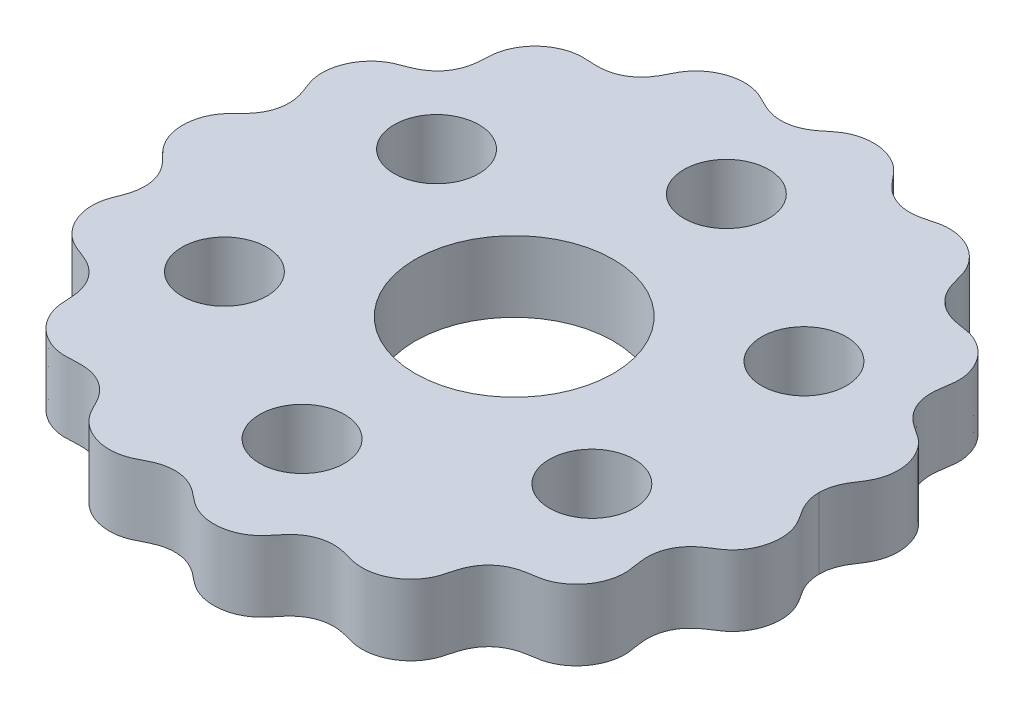
SolidWorks part; units mm, degrees
ref_plane "Front Plane" through (0, 0, 0) normal (0, 0, 1) x (1, 0, 0)
ref_plane "Top Plane" through (0, 0, 0) normal (0, 1, 0) x (1, 0, 0)
ref_plane "Right Plane" through (0, 0, 0) normal (1, 0, 0) x (0, 0, -1)
sketch "Sketch1" plane through (0, 0, 0) normal (0, 1, 0) x (1, 0, 0)
  spline S0 degree 4 poles (44.5984, 12.4944) (44.832, 12.1879) (45.2512, 11.5384) (45.7237, 10.4856) (45.9984, 9.1724) (46.03, 8.0346) (45.9105, 7.0216) (45.7203, 6.2632) (45.4573, 5.5829) (45.1464, 4.9823) (44.8648, 4.5205) (44.5648, 4.0709) (44.2669, 3.6199) (44.0083, 3.1913) (43.7929, 2.7844) (43.6185, 2.4022) (43.4802, 2.0484) (43.3629, 1.687) (43.2797, 1.3651) (43.2227, 1.0859) (43.1851, 0.8518) (43.1609, 0.6624) (43.145, 0.4992) (43.1351, 0.3578) (43.1294, 0.2322) (43.1264, 0.1298) (43.1245, 0.0125) (43.1252, -0.0782) (43.1286, -0.2195) (43.135, -0.3523) (43.1419, -0.4548) (43.1529, -0.582) (43.1699, -0.7377) (43.1951, -0.92) (43.231, -1.126) (43.274, -1.3311) (43.3366, -1.5852) (43.4549, -1.9872) (43.66, -2.5262) (44.0033, -3.2085) (44.4867, -3.963) (45.0117, -4.7244) (45.4649, -5.567) (45.8298, -6.5835) (46.0376, -7.77) (46.0189, -9.1082) (45.6992, -10.542) (45.1324, -11.7906) (44.3914, -12.8211) (43.5537, -13.6249) (42.6868, -14.2187) (41.8472, -14.7237) (41.113, -15.2701) (40.3565, -15.9849) (39.644, -16.9209) (39.0655, -18.1762) (38.8218, -19.6149) (38.8837, -20.8087) (39.0365, -21.7287) (39.15, -22.395) (39.2185, -22.9317) (39.2565, -23.6072) (39.2077, -24.5293) (38.9566, -25.6753) (38.3836, -26.9664) (37.4913, -28.188) (36.4562, -29.1122) (35.3715, -29.7513) (34.3004, -30.1449) (33.2968, -30.3406) (32.3424, -30.4567) (31.4554, -30.643) (30.6507, -30.9105) (29.9366, -31.2505) (29.1129, -31.7819) (28.2521, -32.581) (27.6169, -33.5017) (27.1961, -34.4634) (26.9571, -35.2233) (26.8167, -35.7523) (26.6832, -36.2827) (26.5312, -36.8085) (26.2971, -37.4517) (25.8833, -38.2906) (25.1883, -39.2563) (24.1248, -40.2304) (22.7782, -41.008) (21.4029, -41.4417) (20.2189, -41.5611) (19.2857, -41.4995) (18.4763, -41.358) (17.6848, -41.1398) (16.6569, -40.8411) (15.3426, -40.6571) (13.8913, -40.7732) (12.5919, -41.238) (11.5918, -41.8684) (10.8098, -42.5627) (10.2051, -43.2377) (9.6272, -44.0062) (8.9561, -44.7774) (8.0796, -45.5082) (6.9838, -46.1281) (5.6659, -46.5624) (4.1618, -46.7244) (2.7571, -46.5751) (1.6391, -46.2195) (0.8162, -45.8007) (0.2502, -45.4301) (-0.1804, -45.1024) (-0.7006, -44.671) (-1.421, -44.0787) (-2.4239, -43.4281) (-3.7917, -42.9198) (-5.168, -42.7932) (-6.3349, -42.9422) (-7.3322, -43.24) (-8.1725, -43.6026) (-9.0297, -44.0772) (-9.9774, -44.531) (-11.0923, -44.8546) (-12.3553, -44.9811) (-13.7375, -44.8459) (-15.1718, -44.3905) (-16.3918, -43.6927) (-17.2693, -42.9227) (-17.8533, -42.2132) (-18.2222, -41.6499) (-18.4839, -41.1793) (-18.7839, -40.5772) (-19.1955, -39.7455) (-19.8345, -38.7424) (-20.8622, -37.7122) (-22.2286, -36.9233) (-23.6346, -36.5484) (-24.8229, -36.4966) (-25.7489, -36.5559) (-26.4204, -36.5972) (-26.9588, -36.6058) (-27.631, -36.5681) (-28.5375, -36.417) (-29.643, -36.0421) (-30.8574, -35.3344) (-31.969, -34.32) (-32.7771, -33.1905) (-33.2991, -32.0336) (-33.5763, -30.9061) (-33.6571, -29.8585) (-33.6747, -28.8788) (-33.7808, -27.9699) (-34.0216, -26.9573) (-34.476, -25.8723) (-35.2738, -24.7436) (-36.3979, -23.8132) (-37.4628, -23.2699) (-38.3359, -22.9423) (-38.9696, -22.7074) (-39.4687, -22.4983) (-40.0727, -22.1935) (-40.8469, -21.6902) (-41.7138, -20.8998) (-42.5454, -19.758) (-43.1572, -18.3744) (-43.44, -17.0159) (-43.4511, -15.757) (-43.2564, -14.6325) (-42.9241, -13.6656) (-42.5475, -12.7809) (-42.2653, -11.9197) (-42.055, -10.8955) (-42.0167, -9.9082) (-42.1512, -8.933) (-42.4518, -8.0043) (-42.7822, -7.3039) (-43.24, -6.5824) (-43.8372, -5.8614) (-44.4706, -5.2544) (-45.0553, -4.6782) (-45.4944, -4.1525) (-45.8114, -3.7063) (-46.0684, -3.2686) (-46.2741, -2.8497) (-46.4358, -2.4552) (-46.5617, -2.0905) (-46.6535, -1.7655) (-46.7191, -1.4838) (-46.7651, -1.2471) (-46.7966, -1.0568) (-46.8229, -0.866) (-46.8439, -0.6732) (-46.8577, -0.507) (-46.8662, -0.3636) (-46.8712, -0.2362) (-46.8738, -0.132) (-46.8754, -0.0158) (-46.8748, 0.091) (-46.8703, 0.2911) (-46.8602, 0.4745) (-46.8449, 0.6629) (-46.8245, 0.8522) (-46.7991, 1.0403) (-46.7685, 1.2276) (-46.724, 1.4607) (-46.6604, 1.7382) (-46.5715, 2.0584) (-46.4496, 2.4181) (-46.2927, 2.8077) (-46.0929, 3.2223) (-45.843, 3.6565) (-45.5342, 4.1002) (-45.1056, 4.6236) (-44.5323, 5.1972) (-43.9, 5.7965) (-43.2951, 6.5085) (-42.8248, 7.2269) (-42.4804, 7.9319) (-42.1599, 8.8828) (-42.0135, 9.8922) (-42.0547, 10.922) (-42.228, 11.7337) (-42.3436, 12.1315) (-42.4074, 12.3284) knots 0 0 0 0 0 0.008419 0.016837 0.025005 0.029089 0.033173 0.039077 0.042029 0.044981 0.047933 0.050885 0.053837 0.056789 0.058863 0.060937 0.063011 0.065085 0.067158 0.068195 0.069232 0.070269 0.071306 0.071825 0.072343 0.072861 0.07338 0.074472 0.075017 0.075563 0.076135 0.076707 0.07785 0.078994 0.080138 0.081281 0.082425 0.084712 0.089287 0.093861 0.099069 0.104277 0.109486 0.114694 0.122573 0.130452 0.138512 0.146571 0.152296 0.158021 0.163745 0.16947 0.173713 0.177956 0.186442 0.195001 0.203561 0.209467 0.212421 0.215374 0.218327 0.22128 0.227187 0.235488 0.24379 0.251894 0.259998 0.265567 0.271137 0.276706 0.282275 0.286582 0.290889 0.295197 0.299504 0.307939 0.316375 0.319362 0.32235 0.325338 0.328326 0.331314 0.334302 0.340277 0.348703 0.357129 0.365555 0.373981 0.379956 0.382944 0.385932 0.391908 0.397883 0.406319 0.414754 0.423368 0.427675 0.431982 0.437552 0.443121 0.44869 0.45426 0.462364 0.470468 0.478769 0.487071 0.492978 0.495931 0.498884 0.501837 0.50479 0.510697 0.519257 0.527816 0.536302 0.540545 0.544788 0.550513 0.556237 0.561962 0.567686 0.575746 0.583806 0.592068 0.60033 0.606208 0.609147 0.612086 0.615025 0.617964 0.623842 0.63236 0.640878 0.649396 0.657914 0.663792 0.666731 0.66967 0.672609 0.675548 0.681426 0.689688 0.69795 0.70601 0.714069 0.719794 0.725519 0.731243 0.736968 0.741211 0.745454 0.75394 0.762499 0.771059 0.776965 0.779919 0.782872 0.785825 0.788778 0.794685 0.802986 0.811288 0.819392 0.827496 0.833065 0.838635 0.844204 0.849773 0.85408 0.858388 0.867002 0.871219 0.875437 0.879655 0.883873 0.889848 0.895824 0.898812 0.9018 0.904787 0.907775 0.909882 0.911988 0.914095 0.916201 0.917254 0.918308 0.919361 0.920414 0.921467 0.92252 0.923047 0.923574 0.9241 0.924627 0.925664 0.9267 0.927737 0.928773 0.92981 0.930846 0.931883 0.93292 0.934993 0.937066 0.939139 0.941212 0.944163 0.947114 0.950065 0.953016 0.958918 0.96482 0.969093 0.973365 0.977638 0.981911 0.990955 0.995478 1 1 1 1 1 construction
  spline S1 degree 4 poles (43.125, 0) (43.125, -0.0425) (43.1258, -0.1053) (43.1286, -0.2195) (43.135, -0.3523) (43.1419, -0.4548) (43.1529, -0.582) (43.1699, -0.7377) (43.1951, -0.92) (43.231, -1.126) (43.274, -1.3311) (43.3366, -1.5852) (43.4549, -1.9872) (43.66, -2.5262) (44.0033, -3.2085) (44.4867, -3.963) (45.0117, -4.7244) (45.4649, -5.567) (45.8298, -6.5835) (46.0376, -7.77) (46.0189, -9.1082) (45.6992, -10.542) (45.1324, -11.7906) (44.3914, -12.8211) (43.5537, -13.6249) (42.6868, -14.2187) (41.8472, -14.7237) (41.113, -15.2701) (40.3565, -15.9849) (39.644, -16.9209) (39.0655, -18.1762) (38.8218, -19.6149) (38.8837, -20.8087) (39.0365, -21.7287) (39.15, -22.395) (39.2185, -22.9317) (39.2565, -23.6072) (39.2077, -24.5293) (38.9566, -25.6753) (38.3836, -26.9664) (37.4913, -28.188) (36.4562, -29.1122) (35.3715, -29.7513) (34.3004, -30.1449) (33.2968, -30.3406) (32.3424, -30.4567) (31.4554, -30.643) (30.6507, -30.9105) (29.9366, -31.2505) (29.1129, -31.7819) (28.2521, -32.581) (27.6169, -33.5017) (27.1961, -34.4634) (26.9571, -35.2233) (26.8167, -35.7523) (26.6832, -36.2827) (26.5312, -36.8085) (26.2971, -37.4517) (25.8833, -38.2906) (25.1883, -39.2563) (24.1248, -40.2304) (22.7782, -41.008) (21.4029, -41.4417) (20.2189, -41.5611) (19.2857, -41.4995) (18.4763, -41.358) (17.6848, -41.1398) (16.6569, -40.8411) (15.3426, -40.6571) (13.8913, -40.7732) (12.5919, -41.238) (11.5918, -41.8684) (10.8098, -42.5627) (10.2051, -43.2377) (9.6272, -44.0062) (8.9561, -44.7774) (8.0796, -45.5082) (6.9838, -46.1281) (5.6659, -46.5624) (4.1618, -46.7244) (2.7571, -46.5751) (1.6391, -46.2195) (0.8162, -45.8007) (0.2502, -45.4301) (-0.1804, -45.1024) (-0.7006, -44.671) (-1.421, -44.0787) (-2.4239, -43.4281) (-3.7917, -42.9198) (-5.168, -42.7932) (-6.3349, -42.9422) (-7.3322, -43.24) (-8.1725, -43.6026) (-9.0297, -44.0772) (-9.9774, -44.531) (-11.0923, -44.8546) (-12.3553, -44.9811) (-13.7375, -44.8459) (-15.1718, -44.3905) (-16.3918, -43.6927) (-17.2693, -42.9227) (-17.8533, -42.2132) (-18.2222, -41.6499) (-18.4839, -41.1793) (-18.7839, -40.5772) (-19.1955, -39.7455) (-19.8345, -38.7424) (-20.8622, -37.7122) (-22.2286, -36.9233) (-23.6346, -36.5484) (-24.8229, -36.4966) (-25.7489, -36.5559) (-26.4204, -36.5972) (-26.9588, -36.6058) (-27.631, -36.5681) (-28.5375, -36.417) (-29.643, -36.0421) (-30.8574, -35.3344) (-31.969, -34.32) (-32.7771, -33.1905) (-33.2991, -32.0336) (-33.5763, -30.9061) (-33.6571, -29.8585) (-33.6747, -28.8788) (-33.7808, -27.9699) (-34.0216, -26.9573) (-34.476, -25.8723) (-35.2738, -24.7436) (-36.3979, -23.8132) (-37.4628, -23.2699) (-38.3359, -22.9423) (-38.9696, -22.7074) (-39.4687, -22.4983) (-40.0727, -22.1935) (-40.8469, -21.6902) (-41.7138, -20.8998) (-42.5454, -19.758) (-43.1572, -18.3744) (-43.44, -17.0159) (-43.4511, -15.757) (-43.2564, -14.6325) (-42.9241, -13.6656) (-42.5475, -12.7809) (-42.2653, -11.9197) (-42.055, -10.8955) (-42.0167, -9.9082) (-42.1512, -8.933) (-42.4518, -8.0043) (-42.7822, -7.3039) (-43.24, -6.5824) (-43.8372, -5.8614) (-44.4706, -5.2544) (-45.0553, -4.6782) (-45.4944, -4.1525) (-45.8114, -3.7063) (-46.0684, -3.2686) (-46.2741, -2.8497) (-46.4358, -2.4552) (-46.5617, -2.0905) (-46.6535, -1.7655) (-46.7191, -1.4838) (-46.7651, -1.2471) (-46.7966, -1.0568) (-46.8229, -0.866) (-46.8439, -0.6732) (-46.8577, -0.507) (-46.8662, -0.3636) (-46.8712, -0.2362) (-46.8738, -0.132) (-46.8748, -0.0619) (-46.875, -0.0205) (-46.875, 0) knots 0.07338 0.07338 0.07338 0.07338 0.07338 0.074472 0.075017 0.075563 0.076135 0.076707 0.07785 0.078994 0.080138 0.081281 0.082425 0.084712 0.089287 0.093861 0.099069 0.104277 0.109486 0.114694 0.122573 0.130452 0.138512 0.146571 0.152296 0.158021 0.163745 0.16947 0.173713 0.177956 0.186442 0.195001 0.203561 0.209467 0.212421 0.215374 0.218327 0.22128 0.227187 0.235488 0.24379 0.251894 0.259998 0.265567 0.271137 0.276706 0.282275 0.286582 0.290889 0.295197 0.299504 0.307939 0.316375 0.319362 0.32235 0.325338 0.328326 0.331314 0.334302 0.340277 0.348703 0.357129 0.365555 0.373981 0.379956 0.382944 0.385932 0.391908 0.397883 0.406319 0.414754 0.423368 0.427675 0.431982 0.437552 0.443121 0.44869 0.45426 0.462364 0.470468 0.478769 0.487071 0.492978 0.495931 0.498884 0.501837 0.50479 0.510697 0.519257 0.527816 0.536302 0.540545 0.544788 0.550513 0.556237 0.561962 0.567686 0.575746 0.583806 0.592068 0.60033 0.606208 0.609147 0.612086 0.615025 0.617964 0.623842 0.63236 0.640878 0.649396 0.657914 0.663792 0.666731 0.66967 0.672609 0.675548 0.681426 0.689688 0.69795 0.70601 0.714069 0.719794 0.725519 0.731243 0.736968 0.741211 0.745454 0.75394 0.762499 0.771059 0.776965 0.779919 0.782872 0.785825 0.788778 0.794685 0.802986 0.811288 0.819392 0.827496 0.833065 0.838635 0.844204 0.849773 0.85408 0.858388 0.867002 0.871219 0.875437 0.879655 0.883873 0.889848 0.895824 0.898812 0.9018 0.904787 0.907775 0.909882 0.911988 0.914095 0.916201 0.917254 0.918308 0.919361 0.920414 0.921467 0.92252 0.923047 0.923574 0.9241 0.924627 0.924627 0.924627 0.924627 0.924627
  spline S2 degree 4 poles (43.125, 0) (43.125, 0.0425) (43.1258, 0.1053) (43.1286, 0.2195) (43.135, 0.3523) (43.1419, 0.4548) (43.1529, 0.582) (43.1699, 0.7377) (43.1951, 0.92) (43.231, 1.126) (43.274, 1.3311) (43.3366, 1.5852) (43.4549, 1.9872) (43.66, 2.5262) (44.0033, 3.2085) (44.4867, 3.963) (45.0117, 4.7244) (45.4649, 5.567) (45.8298, 6.5835) (46.0376, 7.77) (46.0189, 9.1082) (45.6992, 10.542) (45.1324, 11.7906) (44.3914, 12.8211) (43.5537, 13.6249) (42.6868, 14.2187) (41.8472, 14.7237) (41.113, 15.2701) (40.3565, 15.9849) (39.644, 16.9209) (39.0655, 18.1762) (38.8218, 19.6149) (38.8837, 20.8087) (39.0365, 21.7287) (39.15, 22.395) (39.2185, 22.9317) (39.2565, 23.6072) (39.2077, 24.5293) (38.9566, 25.6753) (38.3836, 26.9664) (37.4913, 28.188) (36.4562, 29.1122) (35.3715, 29.7513) (34.3004, 30.1449) (33.2968, 30.3406) (32.3424, 30.4567) (31.4554, 30.643) (30.6507, 30.9105) (29.9366, 31.2505) (29.1129, 31.7819) (28.2521, 32.581) (27.6169, 33.5017) (27.1961, 34.4634) (26.9571, 35.2233) (26.8167, 35.7523) (26.6832, 36.2827) (26.5312, 36.8085) (26.2971, 37.4517) (25.8833, 38.2906) (25.1883, 39.2563) (24.1248, 40.2304) (22.7782, 41.008) (21.4029, 41.4417) (20.2189, 41.5611) (19.2857, 41.4995) (18.4763, 41.358) (17.6848, 41.1398) (16.6569, 40.8411) (15.3426, 40.6571) (13.8913, 40.7732) (12.5919, 41.238) (11.5918, 41.8684) (10.8098, 42.5627) (10.2051, 43.2377) (9.6272, 44.0062) (8.9561, 44.7774) (8.0796, 45.5082) (6.9838, 46.1281) (5.6659, 46.5624) (4.1618, 46.7244) (2.7571, 46.5751) (1.6391, 46.2195) (0.8162, 45.8007) (0.2502, 45.4301) (-0.1804, 45.1024) (-0.7006, 44.671) (-1.421, 44.0787) (-2.4239, 43.4281) (-3.7917, 42.9198) (-5.168, 42.7932) (-6.3349, 42.9422) (-7.3322, 43.24) (-8.1725, 43.6026) (-9.0297, 44.0772) (-9.9774, 44.531) (-11.0923, 44.8546) (-12.3553, 44.9811) (-13.7375, 44.8459) (-15.1718, 44.3905) (-16.3918, 43.6927) (-17.2693, 42.9227) (-17.8533, 42.2132) (-18.2222, 41.6499) (-18.4839, 41.1793) (-18.7839, 40.5772) (-19.1955, 39.7455) (-19.8345, 38.7424) (-20.8622, 37.7122) (-22.2286, 36.9233) (-23.6346, 36.5484) (-24.8229, 36.4966) (-25.7489, 36.5559) (-26.4204, 36.5972) (-26.9588, 36.6058) (-27.631, 36.5681) (-28.5375, 36.417) (-29.643, 36.0421) (-30.8574, 35.3344) (-31.969, 34.32) (-32.7771, 33.1905) (-33.2991, 32.0336) (-33.5763, 30.9061) (-33.6571, 29.8585) (-33.6747, 28.8788) (-33.7808, 27.9699) (-34.0216, 26.9573) (-34.476, 25.8723) (-35.2738, 24.7436) (-36.3979, 23.8132) (-37.4628, 23.2699) (-38.3359, 22.9423) (-38.9696, 22.7074) (-39.4687, 22.4983) (-40.0727, 22.1935) (-40.8469, 21.6902) (-41.7138, 20.8998) (-42.5454, 19.758) (-43.1572, 18.3744) (-43.44, 17.0159) (-43.4511, 15.757) (-43.2564, 14.6325) (-42.9241, 13.6656) (-42.5475, 12.7809) (-42.2653, 11.9197) (-42.055, 10.8955) (-42.0167, 9.9082) (-42.1512, 8.933) (-42.4518, 8.0043) (-42.7822, 7.3039) (-43.24, 6.5824) (-43.8372, 5.8614) (-44.4706, 5.2544) (-45.0553, 4.6782) (-45.4944, 4.1525) (-45.8114, 3.7063) (-46.0684, 3.2686) (-46.2741, 2.8497) (-46.4358, 2.4552) (-46.5617, 2.0905) (-46.6535, 1.7655) (-46.7191, 1.4838) (-46.7651, 1.2471) (-46.7966, 1.0568) (-46.8229, 0.866) (-46.8439, 0.6732) (-46.8577, 0.507) (-46.8662, 0.3636) (-46.8712, 0.2362) (-46.8738, 0.132) (-46.8748, 0.0619) (-46.875, 0.0205) (-46.875, 0) knots 0.07338 0.07338 0.07338 0.07338 0.07338 0.074472 0.075017 0.075563 0.076135 0.076707 0.07785 0.078994 0.080138 0.081281 0.082425 0.084712 0.089287 0.093861 0.099069 0.104277 0.109486 0.114694 0.122573 0.130452 0.138512 0.146571 0.152296 0.158021 0.163745 0.16947 0.173713 0.177956 0.186442 0.195001 0.203561 0.209467 0.212421 0.215374 0.218327 0.22128 0.227187 0.235488 0.24379 0.251894 0.259998 0.265567 0.271137 0.276706 0.282275 0.286582 0.290889 0.295197 0.299504 0.307939 0.316375 0.319362 0.32235 0.325338 0.328326 0.331314 0.334302 0.340277 0.348703 0.357129 0.365555 0.373981 0.379956 0.382944 0.385932 0.391908 0.397883 0.406319 0.414754 0.423368 0.427675 0.431982 0.437552 0.443121 0.44869 0.45426 0.462364 0.470468 0.478769 0.487071 0.492978 0.495931 0.498884 0.501837 0.50479 0.510697 0.519257 0.527816 0.536302 0.540545 0.544788 0.550513 0.556237 0.561962 0.567686 0.575746 0.583806 0.592068 0.60033 0.606208 0.609147 0.612086 0.615025 0.617964 0.623842 0.63236 0.640878 0.649396 0.657914 0.663792 0.666731 0.66967 0.672609 0.675548 0.681426 0.689688 0.69795 0.70601 0.714069 0.719794 0.725519 0.731243 0.736968 0.741211 0.745454 0.75394 0.762499 0.771059 0.776965 0.779919 0.782872 0.785825 0.788778 0.794685 0.802986 0.811288 0.819392 0.827496 0.833065 0.838635 0.844204 0.849773 0.85408 0.858388 0.867002 0.871219 0.875437 0.879655 0.883873 0.889848 0.895824 0.898812 0.9018 0.904787 0.907775 0.909882 0.911988 0.914095 0.916201 0.917254 0.918308 0.919361 0.920414 0.921467 0.92252 0.923047 0.923574 0.9241 0.924627 0.924627 0.924627 0.924627 0.924627
extrude "Boss-Extrude1" add sketch "Sketch1" along normal blind 10 contours S2 S1
sketch "Sketch2" plane through (0, 10, 0) normal (0, 1, 0) x (1, 0, 0)
  circle A0 centre (0, 0) radius 14
  circle A1 centre (0, 30) radius 6
  circle A2 centre (25.9808, 15) radius 6
  circle A3 centre (25.9808, -15) radius 6
  circle A4 centre (0, -30) radius 6
  circle A5 centre (-25.9808, -15) radius 6
  circle A6 centre (-25.9808, 15) radius 6
  point P17 (0, 0)
  dimension "D1" = 28
  dimension "D2" = 12
  dimension "D3" = 30
  dimension "D4" = 6
extrude "Cut-Extrude1" cut sketch "Sketch2" against normal blind 10
